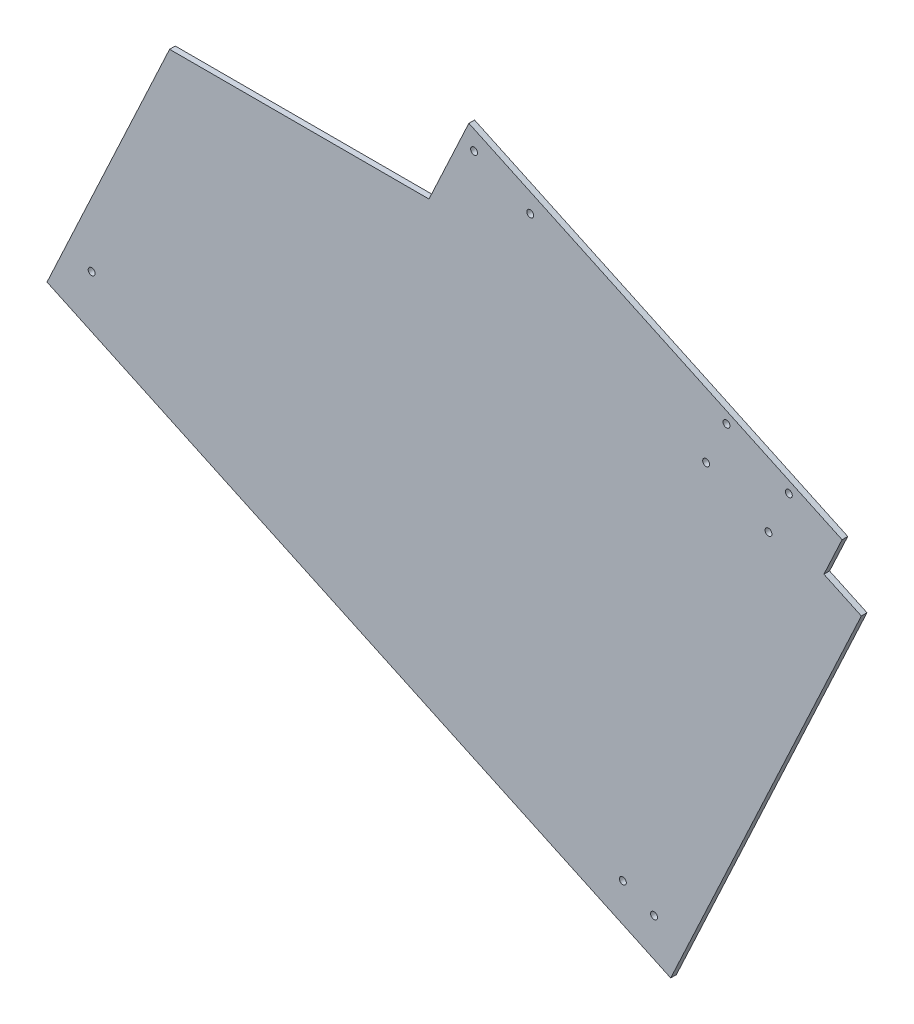
SolidWorks part; units mm, degrees
material "Balsa"
ref_plane "Front Plane" through (0, 0, 0) normal (0, 0, 1) x (1, 0, 0)
ref_plane "Top Plane" through (0, 0, 0) normal (0, 1, 0) x (1, 0, 0)
ref_plane "Right Plane" through (0, 0, 0) normal (1, 0, 0) x (0, 0, -1)
sketch "Sketch1" plane through (0, 0, 0) normal (0, 0, 1) x (1, 0, 0)
  line L0 (-261.1014, 0.0035) -> (-110.3324, 0.0035)
  line L1 (-110.3324, 0.0035) -> (-87.1479, 49.7228)
  line L2 (-87.1479, 49.7228) -> (129.7831, -51.4338)
  line L3 (129.7831, -51.4338) -> (119.2177, -74.0915)
  line L4 (119.2177, -74.0915) -> (140.969, -84.2344)
  line L5 (140.969, -84.2344) -> (30.1585, -321.8683)
  line L6 (30.1585, -321.8683) -> (-332.3646, -152.8209)
  line L7 (-332.3646, -152.8209) -> (-261.1014, 0.0035)
  line L8 (-257.4117, 0.0035) -> (-57.4117, 0.0035) construction
  line L9 (-332.3646, -152.8209) -> (-261.0998, 0.0069) construction
  line L10 (30.1585, -321.8683) -> (-332.3646, -152.8209) construction
  line L11 (140.969, -84.2344) -> (30.1585, -321.8683) construction
  line L12 (-189.2372, 97.3278) -> (129.7831, -51.4338) construction
  line L13 (119.2177, -74.0915) -> (140.969, -84.2344) construction
  line L14 (129.7831, -51.4338) -> (119.2177, -74.0915) construction
  line L15 (-110.3324, 0.0035) -> (-87.1479, 49.7228) construction
  circle A0 centre (87.0035, -69.0002) radius 2
  circle A1 centre (98.8369, -43.6236) radius 2
  circle A2 centre (62.5845, -26.7189) radius 2
  circle A3 centre (50.7512, -52.0955) radius 2
  circle A4 centre (2.3586, -286.8374) radius 2
  circle A5 centre (-306.4229, -134.5749) radius 2
  circle A6 centre (20.4847, -295.2897) radius 2
  circle A7 centre (2.3586, -286.8374) radius 2 construction
  circle A8 centre (20.4847, -295.2897) radius 2 construction
  dimension "D1" = 4
  dimension "D2" = 4
  dimension "D3" = 4
  dimension "D4" = 4
  dimension "D7" = 4
  dimension "D5" = 27.5
  dimension "D6" = 15.8
extrude "Boss-Extrude1" add sketch "Sketch1" along normal up to surface (3.3 mm away)
sketch "Sketch2" plane through (0, 0, 0) normal (0, 0, -1) x (-1, 0, 0)
  line L0 (87.1479, 49.7228) -> (110.3324, 0.0035) construction
  line L1 (-129.7831, -51.4338) -> (87.1479, 49.7228) construction
  circle A0 centre (51.4966, 22.0645) radius 2
  circle A1 centre (84.1237, 37.2788) radius 2
  dimension "D1" = 4
  dimension "D2" = 4
  dimension "D3" = 8
  dimension "D4" = 36
  dimension "D5" = 10
  dimension "D6" = 10
extrude "Cut-Extrude1" cut sketch "Sketch2" against normal through all
